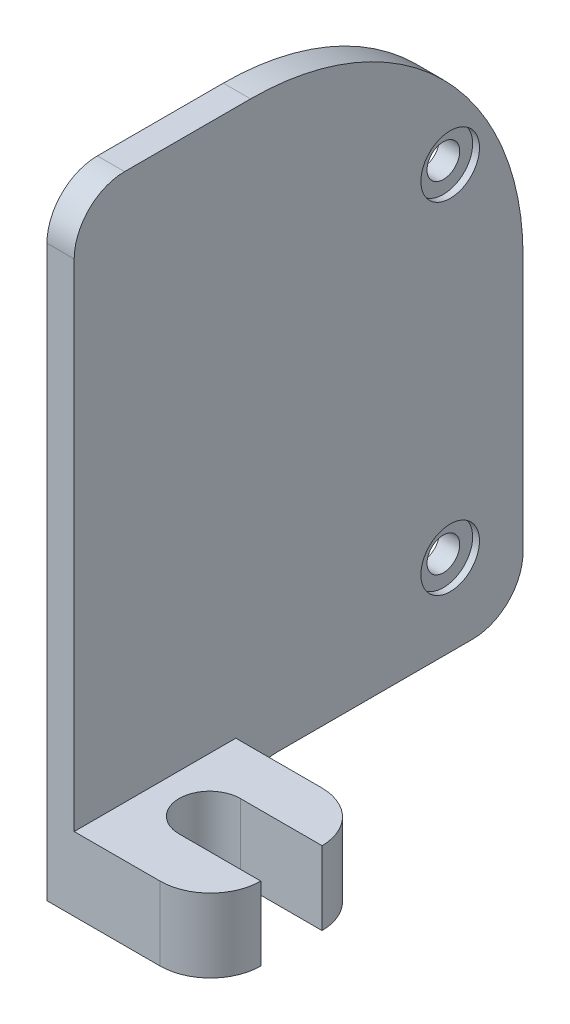
SolidWorks part; units mm, degrees
material "6061 合金"
ref_plane "前视基准面" through (0, 0, 0) normal (0, 0, 1) x (1, 0, 0)
ref_plane "上视基准面" through (0, 0, 0) normal (0, 1, 0) x (1, 0, 0)
ref_plane "右视基准面" through (0, 0, 0) normal (1, 0, 0) x (0, 0, -1)
sketch "草图1" plane through (0, 0, 0) normal (1, 0, 0) x (0, 0, -1)
  line L1 (-19.9481, 26.6633) -> (19.9481, 26.6633)
  line L2 (-19.9481, 26.6633) -> (-19.9481, -26.6633)
  line L3 (-19.9481, -26.6633) -> (19.9481, -26.6633)
  line L4 (19.9481, 26.6633) -> (19.9481, -26.6633)
  line L5 (-19.9481, 26.6633) -> (19.9481, -26.6633) construction
  line L6 (-19.9481, -26.6633) -> (19.9481, 26.6633) construction
  point P0 (0, 0)
extrude "凸台-拉伸1" add sketch "草图1" along normal blind 2
sketch "草图2" plane through (0, -26.6633, 0) normal (0, -1, 0) x (1, 0, 0)
  line L0 (0, -21.9429) -> (0, 21.9429) construction
  line L1 (0, 19.9481) -> (12, 19.9481)
  line L2 (0, 19.9481) -> (0, -19.9156)
  line L3 (0, -19.9156) -> (12, -19.9156)
  line L4 (12, 19.9481) -> (12, -19.9156)
  line L5 (2, 19.9481) -> (0, 19.9481) construction
  dimension "D1" = 12
extrude "凸台-拉伸2" add sketch "草图2" against normal blind 10
sketch "草图3" plane through (0, -16.6633, 0) normal (0, 1, 0) x (1, 0, 0)
  line L0 (0, 0) -> (6, 0) construction
  line L3 (6, 0) -> (6, -3.1097) construction
  line L4 (0, 19.9481) -> (0, -19.9481) construction
  dimension "D1" = 6
hole_wizard "打孔尺寸(%根据)内六角圆柱头螺钉的类型1" positions "3D草图2" profile "草图5" counterbore size "M4" standard "GB" end condition through all
sketch3d "3D草图2"
  point P0 (6, -16.6633, 0)
sketch "草图5" plane through (6, -16.6633, 0) normal (1, 0, 0) x (0, 0, 1)
  line L0 (0, 0) -> (0, 10)
  line L1 (0, 10) -> (2.25, 10)
  line L3 (2.25, 10) -> (2.25, 4.6)
  line L4 (2.25, 4.6) -> (4, 4.6)
  line L5 (4, 4.6) -> (4, 0)
  line L7 (4, 0) -> (0, 0)
  line L11 (0, -6.35) -> (0, 107.95) construction
  dimension "通孔孔直径" = 4.5
  dimension "通孔孔深度" = 10
  dimension "柱形沉头孔直径" = 8
  dimension "柱形沉头孔深度" = 4.6
sketch "草图6" plane through (0, -16.6633, 0) normal (0, 1, 0) x (1, 0, 0)
  line L0 (2, 19.9481) -> (2, -19.9481) construction
  line L1 (12, 19.9156) -> (2, 19.9156)
  line L2 (12, 19.9156) -> (12, 5.9156)
  line L3 (12, 5.9156) -> (2, 5.9156)
  line L4 (2, 19.9156) -> (2, 5.9156)
  line L5 (12, -19.9481) -> (2, -19.9481) construction
  line L6 (12, -19.9481) -> (2, -19.9481)
  line L7 (12, -19.9481) -> (12, -5.9481)
  line L8 (12, -5.9481) -> (2, -5.9481)
  line L9 (2, -19.9481) -> (2, -5.9481)
  line L10 (12, 19.9156) -> (12, -19.9481) construction
  dimension "D1" = 14
  dimension "D2" = 14
extrude "切除-拉伸1" cut sketch "草图6" against normal through all
sketch "草图7" plane through (0, 0, 0) normal (-1, 0, 0) x (0, 0, 1)
  line L1 (5.54, 18.8367) -> (-7, 18.8367)
  line L3 (10.54, 13.8367) -> (10.54, 12.4779)
  line L5 (-27, -34.6633) -> (-27, -1.1633)
  circle A2 centre (0, -5.1633) radius 20
  arc A3 (10.54, 13.8367) -> (5.54, 18.8367) centre (5.54, 13.8367) ccw
  arc A5 (-7, 18.8367) -> (-27, -1.1633) centre (-7, -1.1633) ccw
sketch "草图8" plane through (2, 0, 0) normal (1, 0, 0) x (0, 0, -1)
  line L0 (27, -34.6633) -> (27, -1.1633) construction
  line L1 (19.9481, -26.6633) -> (27, -26.6633)
  line L2 (19.9481, -26.6633) -> (19.9481, 26.5164)
  line L3 (19.9481, 26.5164) -> (27, 26.5164)
  line L4 (27, -26.6633) -> (27, 26.5164)
extrude "凸台-拉伸3" add sketch "草图8" against normal up to surface (2 mm away) up to face at (0, 0, 0)
sketch "草图9" plane through (2, 0, 0) normal (1, 0, 0) x (0, 0, -1)
  line L0 (-5.54, 18.8367) -> (7, 18.8367) construction
  line L1 (-5.54, 18.8367) -> (7, 18.8367)
  line L2 (-10.54, 13.8367) -> (-10.54, 11.834)
  line L14 (0, -16.6633) -> (5.9156, -16.6633)
  line L15 (5.9156, -16.6633) -> (5.9156, -26.6633)
  line L16 (5.9156, -26.6633) -> (27, -26.6633)
  line L17 (27, -26.6633) -> (27, 26.5164)
  line L18 (27, 26.5164) -> (19.9481, 26.5164)
  line L19 (19.9481, 26.5164) -> (19.9481, 26.6633)
  line L20 (19.9481, 26.6633) -> (-19.9481, 26.6633)
  line L21 (-19.9481, 26.6633) -> (-19.9481, -26.6633)
  line L22 (-19.9481, -26.6633) -> (-5.9481, -26.6633)
  line L23 (-5.9481, -26.6633) -> (-5.9481, -16.6633)
  line L24 (-5.9481, -16.6633) -> (0, -16.6633)
  line L28 (27, -1.1633) -> (27, 26.5164)
  line L29 (27, 26.5164) -> (19.9481, 26.5164)
  line L30 (19.9481, 26.5164) -> (19.9481, 26.6633)
  line L31 (19.9481, 26.6633) -> (-19.9481, 26.6633)
  line L32 (-19.9481, 26.6633) -> (-19.9481, -26.6633)
  line L33 (-19.9481, -26.6633) -> (-5.9481, -26.6633)
  line L34 (-5.9481, -26.6633) -> (-5.9481, -24.2583)
  arc A0 (27, -1.1633) -> (7, 18.8367) centre (7, -1.1633) ccw construction
  circle A1 centre (0, -5.1633) radius 20 construction
  arc A2 (-5.54, 18.8367) -> (-10.54, 13.8367) centre (-5.54, 13.8367) ccw construction
  arc A3 (27, -1.1633) -> (7, 18.8367) centre (7, -1.1633) ccw
  arc A4 (-10.54, 11.834) -> (-5.9481, -24.2583) centre (0, -5.1633) ccw
  arc A5 (-5.54, 18.8367) -> (-10.54, 13.8367) centre (-5.54, 13.8367) ccw
  line M16 (27, -26.6633) -> (27, 26.5164)
  line M17 (27, 26.5164) -> (19.9481, 26.5164)
  line M18 (19.9481, 26.5164) -> (19.9481, 26.6633)
  line M19 (19.9481, 26.6633) -> (-19.9481, 26.6633)
  line M20 (-19.9481, 26.6633) -> (-19.9481, -26.6633)
  line M21 (-19.9481, -26.6633) -> (-5.9481, -26.6633)
  line M22 (-5.9481, -26.6633) -> (-5.9481, -16.6633)
  dimension "D1" = 0
extrude "切除-拉伸2" cut sketch "草图9" against normal through all contours A5 L1 A3 A4 L2 M16 M17 M18 M19 M20 | A4 M20 M21 M22 region at (2, 19.3659, -2.3668) region at (2, -21.725, 15.1579)
sketch "草图10" plane through (2, 0, 0) normal (1, 0, 0) x (0, 0, -1)
  line L0 (0, -5.1633) -> (21.6506, 7.3367) construction
  line L1 (0, -5.1633) -> (21.6506, -17.6633) construction
  line L2 (5.9156, -26.6633) -> (27, -26.6633) construction
  circle A0 centre (0, -5.1633) radius 25 construction
  dimension "D1" = 30
  dimension "D2" = 60
hole_wizard "打孔尺寸(%根据)内六角圆柱头螺钉的类型2" positions "3D草图3" profile "草图11" counterbore size "M2" standard "GB" end condition through all
sketch3d "3D草图3"
  point P0 (2, 7.3367, -21.6506)
  point P3 (2, -17.6633, -21.6506)
sketch "草图11" plane through (2, 7.3367, -21.6506) normal (0, 1, 0) x (0, 0, -1)
  line L0 (0, 0) -> (0, 2)
  line L1 (0, 2) -> (1.2, 2)
  line L3 (1.2, 2) -> (1.2, 0.5)
  line L4 (1.2, 0.5) -> (2.15, 0.5)
  line L5 (2.15, 0.5) -> (2.15, 0)
  line L7 (2.15, 0) -> (0, 0)
  line L11 (0, -6.35) -> (0, 107.95) construction
  dimension "通孔孔直径" = 2.4
  dimension "通孔孔深度" = 2
  dimension "柱形沉头孔直径" = 4.3
  dimension "柱形沉头孔深度" = 0.5
sketch "草图12" plane through (2, 0, 0) normal (1, 0, 0) x (0, 0, -1)
  line L0 (5.9156, -26.6633) -> (5.9156, -16.6633) construction
  line L1 (27, -26.6633) -> (5.9156, -26.6633)
  line L2 (27, -26.6633) -> (27, -23.6633)
  line L3 (27, -23.6633) -> (5.9156, -23.6633)
  line L4 (5.9156, -26.6633) -> (5.9156, -23.6633)
  dimension "D1" = 3
extrude "切除-拉伸3" cut sketch "草图12" against normal through all
fillet "圆角1" radius 3 1 edges at (1, -23.6633, -5.9156)
sketch "草图13" plane through (2, 0, 0) normal (1, 0, 0) x (0, 0, -1)
  line L1 (-5.9481, -24.2583) -> (-21.4705, -24.2583)
  line L2 (-5.9481, -24.2583) -> (-5.9481, 19.448)
  line L3 (-5.9481, 19.448) -> (-21.4705, 19.448)
  line L4 (-21.4705, -24.2583) -> (-21.4705, 19.448)
extrude "切除-拉伸4" cut sketch "草图13" against normal through all
sketch "草图14" plane through (0, -16.6633, 0) normal (0, 1, 0) x (1, 0, 0)
  line L5 (2, 5.9156) -> (12, 5.9156) construction
  line L6 (12, -5.9481) -> (6, -5.9481)
  line L7 (12, -5.9481) -> (12, 5.9156)
  line L8 (12, 5.9156) -> (6, 5.9156)
  line L9 (6, -5.9481) -> (6, 5.9156)
  line L10 (6, 0) -> (6, -3.1097) construction
extrude "切除-拉伸5" cut sketch "草图14" against normal up to surface (4.6 mm away) up to face at (6, -21.2633, 2.25)
sketch "草图15" plane through (0, -21.2633, 0) normal (0, 1, 0) x (1, 0, 0)
  line L5 (12, -5.9481) -> (12, 5.9156) construction
  line L6 (6, 2.25) -> (12, 2.25)
  line L7 (6, 2.25) -> (6, -2.25)
  line L8 (6, -2.25) -> (12, -2.25)
  line L9 (12, 2.25) -> (12, -2.25)
  circle A1 centre (6, 0) radius 2.25 construction
  dimension "D1" = 0
extrude "切除-拉伸6" cut sketch "草图15" against normal through all
fillet "圆角2" radius 3.7 2 edges at (12, -23.9633, -5.9156) (12, -23.9633, 5.9481)
fillet "圆角3" radius 3.7 2 edges at (1, 18.8201, 5.9481) (1, -23.6633, -27)
sketch "草图17" plane through (6, 0, 0) normal (1, 0, 0) x (0, 0, -1)
  line L1 (-5.9481, -21.2633) -> (5.9156, -21.2633)
  line L2 (-5.9481, -21.2633) -> (-5.9481, -16.6633)
  line L3 (-5.9481, -16.6633) -> (5.9156, -16.6633)
  line L4 (5.9156, -21.2633) -> (5.9156, -16.6633)
extrude "切除-拉伸7" cut sketch "草图17" against normal up to surface (4 mm away) up to face at (2, -7.9575, -8.5839)
